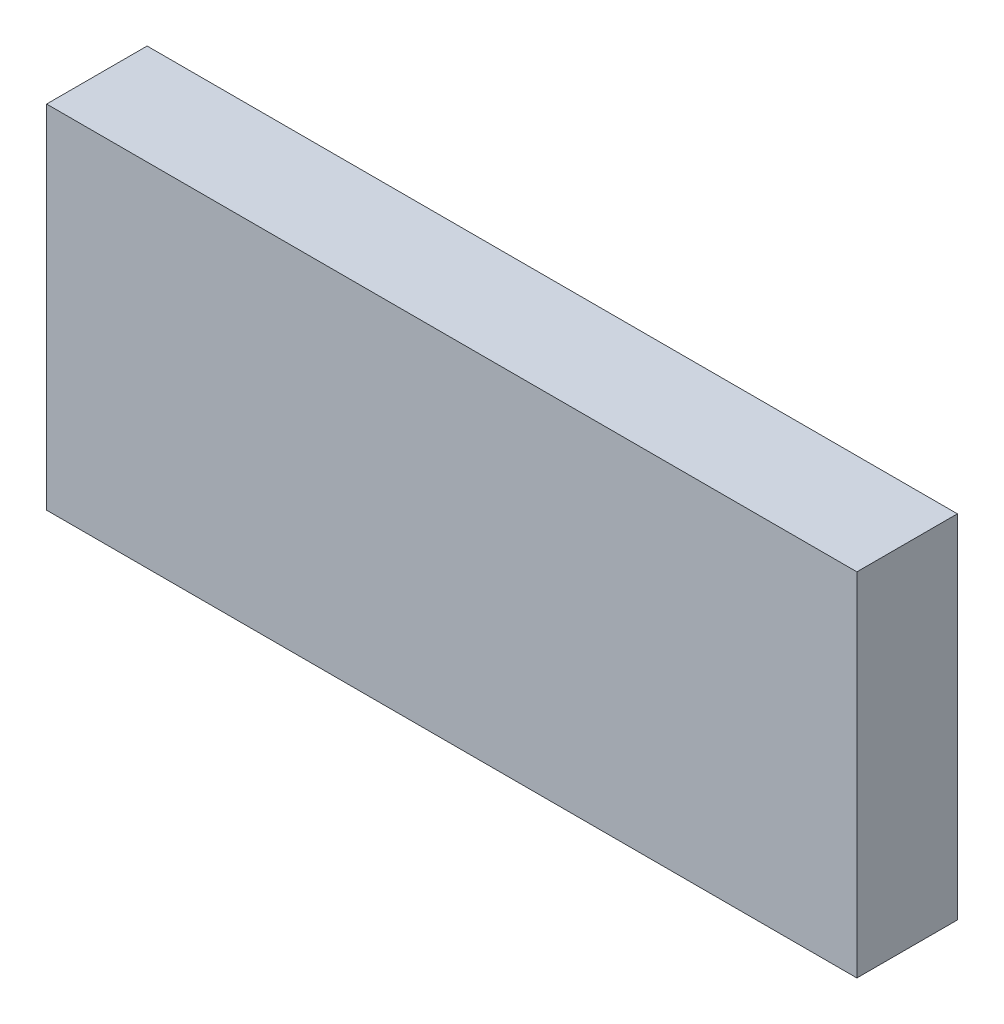
SolidWorks part; units mm, degrees
ref_plane "Front Plane" through (0, 0, 0) normal (0, 0, 1) x (1, 0, 0)
ref_plane "Top Plane" through (0, 0, 0) normal (0, 1, 0) x (1, 0, 0)
ref_plane "Right Plane" through (0, 0, 0) normal (1, 0, 0) x (0, 0, -1)
sketch "Sketch1" plane through (0, 0, 0) normal (0, 0, 1) x (1, 0, 0)
  line L1 (0, 0) -> (819.15, 0)
  line L2 (0, 0) -> (0, 355.6)
  line L3 (0, 355.6) -> (819.15, 355.6)
  line L4 (819.15, 0) -> (819.15, 355.6)
extrude "Boss-Extrude1" add sketch "Sketch1" along normal blind 101.6
sketch "Sketch2" plane through (0, 0, 0) normal (1, 0, 0) x (0, 0, -1)
  circle A0 centre (409.575, 0) radius 2.7686
